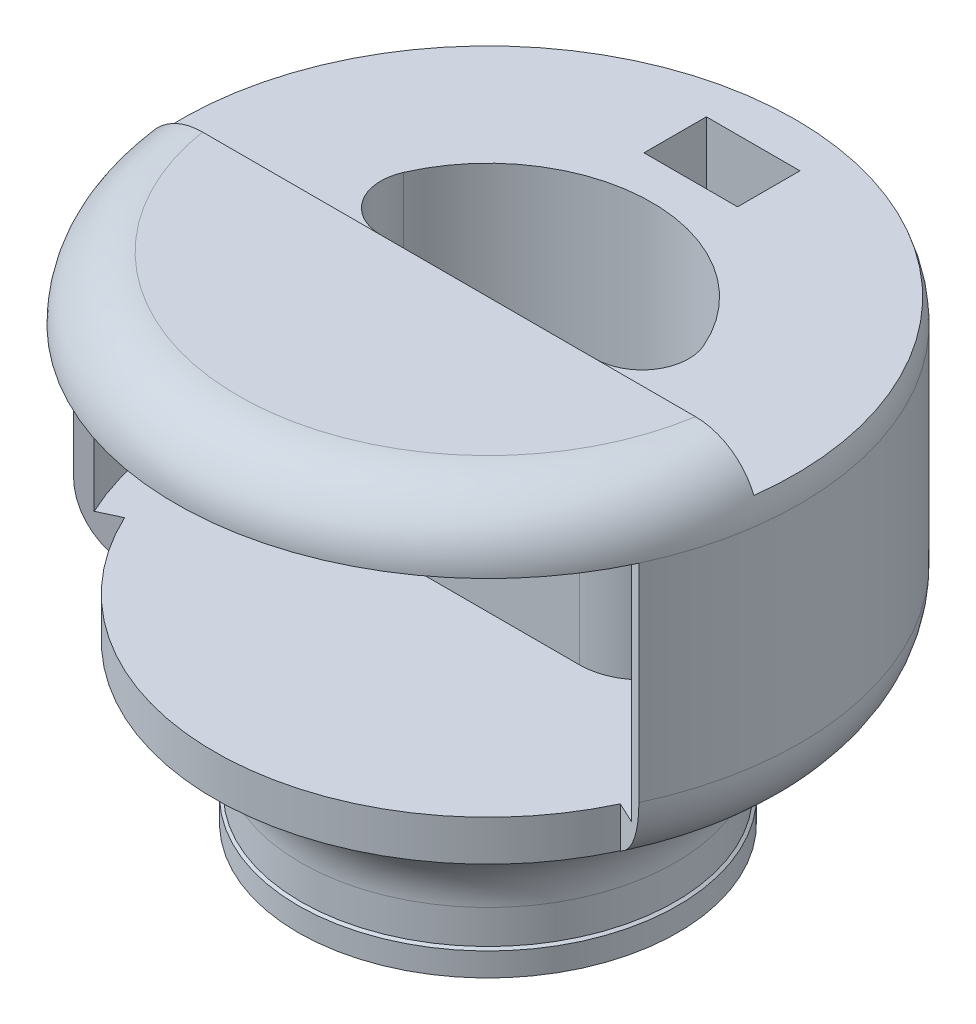
SolidWorks part; units mm, degrees
ref_plane "Front Plane" through (0, 0, 0) normal (0, 0, 1) x (1, 0, 0)
ref_plane "Top Plane" through (0, 0, 0) normal (0, 1, 0) x (1, 0, 0)
ref_plane "Right Plane" through (0, 0, 0) normal (1, 0, 0) x (0, 0, -1)
sketch "Sketch1" plane through (0, 0, 0) normal (0, 0, 1) x (1, 0, 0)
  line L0 (0, 0) -> (0, 90.2242) construction
  line L28 (0, 63.4279) -> (32, 63.4279)
  line L29 (40, 55.4279) -> (40, 28.8468)
  line L30 (22.5, 0) -> (24.35, 0)
  line L31 (24.35, 0) -> (24.35, 3)
  line L32 (24.35, 3) -> (24, 3.25)
  line L33 (24, 3.25) -> (24, 7.5811)
  line L34 (28.5399, 15.9588) -> (35.4601, 20.4691)
  line L35 (0, 13) -> (22, 13)
  line L36 (22.5, 12.5) -> (22.5, 0)
  line L37 (0, 13) -> (0, 63.4279)
  arc A0 (22, 13) -> (22.5, 12.5) centre (22, 12.5) cw
  arc A1 (24, 7.5811) -> (28.5399, 15.9588) centre (34, 7.5811) cw
  arc A2 (35.4601, 20.4691) -> (40, 28.8468) centre (30, 28.8468) ccw
  arc A3 (32, 63.4279) -> (40, 55.4279) centre (32, 55.4279) cw
  point P11 (22.9, 63.4279)
  point P18 (22.5, 13)
  point P21 (24, 13)
  point P24 (40, 23.4279)
  point P27 (40, 63.4279)
  point P28 (28.5604, 23.4279)
  point P31 (22.5, 17)
  dimension "D8" = 9.75
  dimension "D9" = 0.5
  dimension "D4" = 1.85
  dimension "D1" = 22.5
  dimension "D10" = 10
  dimension "D11" = 10
  dimension "D12" = 8
  dimension "D2" = 40
  dimension "D3" = 40
  dimension "D5" = 1.5
  dimension "D6" = 3
  dimension "D7" = 13
revolve "Revolve1" add sketch "Sketch1" angle 360 about L0
ref_plane "Plane1" through (0, 13, 0) normal (0, -1, 0) x (-1, 0, 0)
sketch "Sketch18" plane through (0, 0, 0) normal (0, 0, 1) x (1, 0, 0)
  line L0 (0, 0) -> (0, 101.5813) construction
  line L1 (-24.35, 0) -> (24.35, 0) construction
sketch "Sketch3" plane through (0, 0, 0) normal (0, 0, 1) x (1, 0, 0)
  point P0 (1.2404, 19.1989)
ref_point "Point1"
ref_plane "Plane2" through (0, 0, 22.9) normal (0, 0, 1) x (1, 0, 0)
ref_plane "Plane3" through (0, 0, 40) normal (0, 0, 1) x (1, 0, 0)
ref_plane "Plane4" through (0, 55.4279, 0) normal (0, 1, 0) x (1, 0, 0)
sketch "Sketch9" plane through (0, 55.4279, 0) normal (0, 1, 0) x (1, 0, 0)
  circle A7 centre (0, 0) radius 38
  circle A8 centre (0, 0) radius 40 construction
  circle A9 centre (0, 0) radius 23
  dimension "D1" = 2
  dimension "D2" = 46
ref_plane "Plane5" through (0, 13, 0) normal (0, -1, 0) x (-1, 0, 0)
sketch "Sketch11" plane through (0, 13, 0) normal (0, -1, 0) x (-1, 0, 0)
  line L0 (-21, 0) -> (21, 0)
  arc A1 (-21, 0) -> (21, 0) centre (0, 0) cw
  dimension "D1" = 42
extrude "Cut-Extrude3" cut sketch "Sketch11" against normal blind 60
ref_plane "Plane6" through (0, 0, -40) normal (0, 0, -1) x (-1, 0, 0)
extrude "Cut-Extrude5" cut sketch "Sketch9" against normal blind 30 and the other way blind 2
sketch "Sketch19" plane through (0, 0, 0) normal (1, 0, 0) x (0, 0, -1)
  line L0 (-47.0647, 55.4279) -> (-35.0647, 55.4279)
  line L1 (31.2976, 55.4279) -> (-31.2976, 55.4279) construction
  line L2 (-35.0647, 55.4279) -> (-35.0647, 18.9279)
  line L3 (-35.0647, 18.9279) -> (-47.0647, 18.9279)
  line L4 (-47.0647, 18.9279) -> (-47.0647, 55.4279)
  dimension "D1" = 12
  dimension "D2" = 36.5
revolve "Cut-Revolve2" cut sketch "Sketch19" angle 65 about L0 other way angle 65
ref_plane "Plane7" through (0, 0, 22.5) normal (0, 0, -1) x (-1, 0, 0)
sketch "Sketch21" plane through (0, 0, 22.5) normal (0, 0, -1) x (-1, 0, 0)
  line L0 (0, 0) -> (0, 101.5813) construction
  line L1 (-1.625, 4) -> (1.625, 4)
  line L2 (-1.625, 4) -> (-1.625, 0)
  line L3 (-1.625, 0) -> (1.625, 0)
  line L4 (1.625, 4) -> (1.625, 0)
  line L5 (-1.625, 4) -> (1.625, 0) construction
  line L6 (-1.625, 0) -> (1.625, 4) construction
  line L7 (-22.5, 0) -> (22.5, 0) construction
  point P0 (0, 2)
  dimension "D1" = 4
  dimension "D2" = 3.25
extrude "Boss-Extrude3" add sketch "Sketch21" along normal blind 1.35
pattern_circular "CirPattern1" count 5 over 360 about axis through (0, 0, 0) along (0, -1, 0) of "Boss-Extrude3"
ref_plane "Plane8" through (0, 20.4691, 0) normal (0, 1, 0) x (1, 0, 0)
sketch "Sketch22" plane through (0, 63.4279, 0) normal (0, 1, 0) x (1, 0, 0)
  line L0 (-40, 0) -> (40, 0)
  arc A0 (-40, 0) -> (40, 0) centre (0, 0) cw
  arc A1 (36.2523, -16.9047) -> (-36.2523, -16.9047) centre (0, 0) ccw construction
extrude "Cut-Extrude9" cut sketch "Sketch22" against normal blind 5
sketch "Sketch23" plane through (0, 0, -40) normal (0, 0, -1) x (-1, 0, 0)
  line L0 (0, 0) -> (0, 101.5813) construction
  line L1 (31.2976, 55.4279) -> (-31.2976, 55.4279) construction
  circle A0 centre (0, 42.1379) radius 10.5
  dimension "D1" = 21
  dimension "D2" = 13.29
extrude "Cut-Extrude10" cut sketch "Sketch23" against normal blind 10
sketch "Sketch24" plane through (0, 58.4279, 0) normal (0, 1, 0) x (1, 0, 0)
  line L1 (-8.5, 36) -> (8.5, 36)
  line L2 (-8.5, 36) -> (-8.5, 24)
  line L3 (-8.5, 24) -> (8.5, 24)
  line L4 (8.5, 36) -> (8.5, 24)
  line L5 (-8.5, 36) -> (8.5, 24) construction
  line L6 (-8.5, 24) -> (8.5, 36) construction
  arc A0 (39.4162, 0) -> (-39.4162, 0) centre (0, 0) ccw construction
  point P0 (0, 30)
  dimension "D1" = 30
  dimension "D2" = 12
  dimension "D3" = 17
extrude "Boss-Extrude4" add sketch "Sketch24" against normal blind 8
sketch "Sketch26" plane through (0, 58.4279, 0) normal (0, 1, 0) x (1, 0, 0)
  line L1 (-6, 34) -> (6, 34)
  line L2 (-6, 34) -> (-6, 26)
  line L3 (-6, 26) -> (6, 26)
  line L4 (6, 34) -> (6, 26)
  line L5 (-6, 34) -> (6, 26) construction
  line L6 (-6, 26) -> (6, 34) construction
  arc A0 (39.4162, 0) -> (-39.4162, 0) centre (0, 0) ccw construction
  point P0 (0, 30)
  dimension "D1" = 30
  dimension "D2" = 8
  dimension "D3" = 12
extrude "Cut-Extrude11" cut sketch "Sketch26" against normal blind 10
sketch "Sketch27" plane through (8.5, 0, 0) normal (1, 0, 0) x (0, 0, -1)
  line L0 (36, 50.4279) -> (36, 57.4279) construction
  line L1 (27.5, 56.4279) -> (31.5, 56.4279)
  line L2 (27.5, 56.4279) -> (27.5, 51.4279)
  line L3 (27.5, 51.4279) -> (31.5, 51.4279)
  line L4 (31.5, 56.4279) -> (31.5, 51.4279)
  line L5 (27.5, 56.4279) -> (31.5, 51.4279) construction
  line L6 (27.5, 51.4279) -> (31.5, 56.4279) construction
  line L7 (24, 50.4279) -> (24, 57.4279) construction
  line L8 (24, 50.4279) -> (36, 50.4279) construction
  point P0 (29.5, 53.9279)
  dimension "D1" = 12
  dimension "D2" = 3.5
  dimension "D3" = 5
  dimension "D4" = 4
  dimension "D5" = 5.5
extrude "Cut-Extrude12" cut sketch "Sketch27" against normal blind 5
ref_plane "Plane10" through (0, 58.4279, 0) normal (0, 1, 0) x (1, 0, 0)
sketch "Sketch28" plane through (0, 55.4279, 0) normal (0, 1, 0) x (1, 0, 0)
  line L0 (-22.9129, -2) -> (22.9129, -2)
  arc A0 (-22.9129, -2) -> (22.9129, -2) centre (0, 0) ccw
  dimension "D1" = 46
  dimension "D2" = 2
extrude "Cut-Extrude14" cut sketch "Sketch28" against normal blind 30 and the other way blind 2
sketch "Sketch29" plane through (0, 0, 0) normal (0, 0, -1) x (-1, 0, 0)
  line L0 (0, 0) -> (0, 101.5813) construction
  line L1 (32, 63.4279) -> (-32, 63.4279) construction
  circle A0 centre (-30.4162, 60.9279) radius 1
  circle A1 centre (30.4162, 60.9279) radius 1
  circle A2 centre (0, 60.9279) radius 1
  dimension "D1" = 2
  dimension "D2" = 2
  dimension "D3" = 2
  dimension "D4" = 2.5
  dimension "D5" = 2.5
  dimension "D6" = 2.5
  dimension "D7" = 9
  dimension "D8" = 9
extrude "Cut-Extrude15" cut sketch "Sketch29" against normal blind 15
fillet "Fillet1" radius 6 2 edges at (-21, 35.7139, 0) (21, 35.7139, 0)
fillet "Fillet2" radius 8 2 edges at (22.9129, 41.4279, 2) (-22.9129, 41.4279, 2)
sketch "Sketch30" plane through (0, 63.4279, 0) normal (0, 1, 0) x (1, 0, 0)
  line L0 (-32, 0) -> (32, 0) construction
  line L1 (-49.3805, 0) -> (48.3231, 0)
  line L2 (-49.3805, 0) -> (-49.3805, -5)
  line L3 (-49.3805, -5) -> (48.3231, -5)
  line L4 (48.3231, 0) -> (48.3231, -5)
  dimension "D1" = 5
  dimension "D2" = 0
extrude "Cut-Extrude16" cut sketch "Sketch30" against normal blind 5
